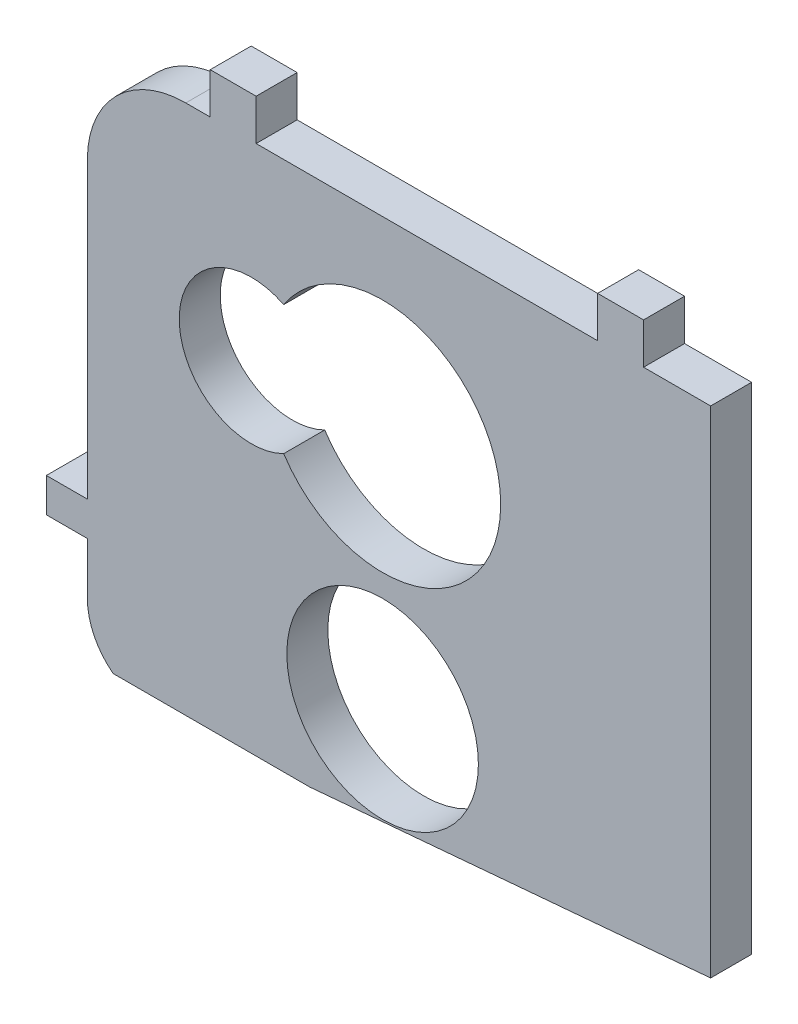
SolidWorks part; units mm, degrees
material "Balsa"
ref_plane "Front Plane" through (0, 0, 0) normal (0, 0, 1) x (1, 0, 0)
ref_plane "Top Plane" through (0, 0, 0) normal (0, 1, 0) x (1, 0, 0)
ref_plane "Right Plane" through (0, 0, 0) normal (1, 0, 0) x (0, 0, -1)
sketch "Sketch1" plane through (0, 0, 0) normal (0, 0, 1) x (1, 0, 0)
  line L0 (0, -1000.1535) -> (0, 48999.8465) construction
  line L1 (-2.8233, -4.0284) -> (-10.4313, -4.0284)
  line L2 (-1000, 0) -> (49000, 0) construction
  line L3 (12.7, 16.51) -> (-7.62, 16.51)
  line L4 (12.7, 16.51) -> (12.7, -2.6702)
  line L5 (8.3256, 18.0975) -> (10.1036, 18.0975)
  line L6 (12.7, -2.6702) -> (-8.6686, -4.5398)
  line L7 (-11.43, 12.7) -> (-11.43, -2.0094)
  line L8 (-6.6744, 16.51) -> (-4.8964, 16.51)
  line L9 (-6.6744, 16.51) -> (-6.6744, 18.0975)
  line L10 (-6.6744, 18.0975) -> (-4.8964, 18.0975)
  line L11 (-4.8964, 16.51) -> (-4.8964, 18.0975)
  line L12 (-11.43, 0) -> (-13.0175, 0)
  line L13 (-11.43, 0) -> (-11.43, 1.3208)
  line L14 (-11.43, 1.3208) -> (-13.0175, 1.3208)
  line L15 (-13.0175, 0) -> (-13.0175, 1.3208)
  line L16 (10.1036, 16.51) -> (10.1036, 18.0975)
  line L17 (8.3256, 16.51) -> (10.1036, 16.51)
  line L18 (8.3256, 16.51) -> (8.3256, 18.0975)
  circle A0 centre (0, 0) radius 3.7084
  arc A1 (-3.829, 6.6457) -> (-3.829, 11.6423) centre (0, 9.144) ccw
  arc A2 (-3.829, 11.6423) -> (-3.829, 6.6457) centre (-5.08, 9.144) ccw
  arc A3 (-7.62, 16.51) -> (-11.43, 12.7) centre (-7.62, 12.7) ccw
  arc A4 (-8.6686, -4.5398) -> (-11.43, -2.0094) centre (-8.89, -2.0094) cw
  dimension "D1" = 7.4168
  dimension "D4" = 7.366
  dimension "D3" = 9.144
  dimension "D5" = 5.588
  dimension "D9" = 3.81
  dimension "D10" = 11.43
  dimension "D14" = 1.5875
  dimension "D12" = 2.54
  dimension "D2" = 12.7
  dimension "D6" = 9.144
  dimension "D7" = 5.08
  dimension "D8" = 6.35
  dimension "D11" = 5
  dimension "D13" = 3.767
  dimension "D15" = 1.778
  dimension "D16" = 1.5875
  dimension "D17" = 1.3208
  dimension "D18" = 1.778
  dimension "D19" = 1.5875
extrude "Boss-Extrude1" add sketch "Sketch1" along normal blind 1.5875 contours A4 L1 L6 L4 L3 A3 L7 A2 A1 A0 | L3 L9 | L18 L3 L16 L5 | L15 L14 L13 L12 region at (-6.6273, -3.7115, 0) region at (9.2146, 17.3037, 0) region at (-5.7854, 17.3037, 0)
